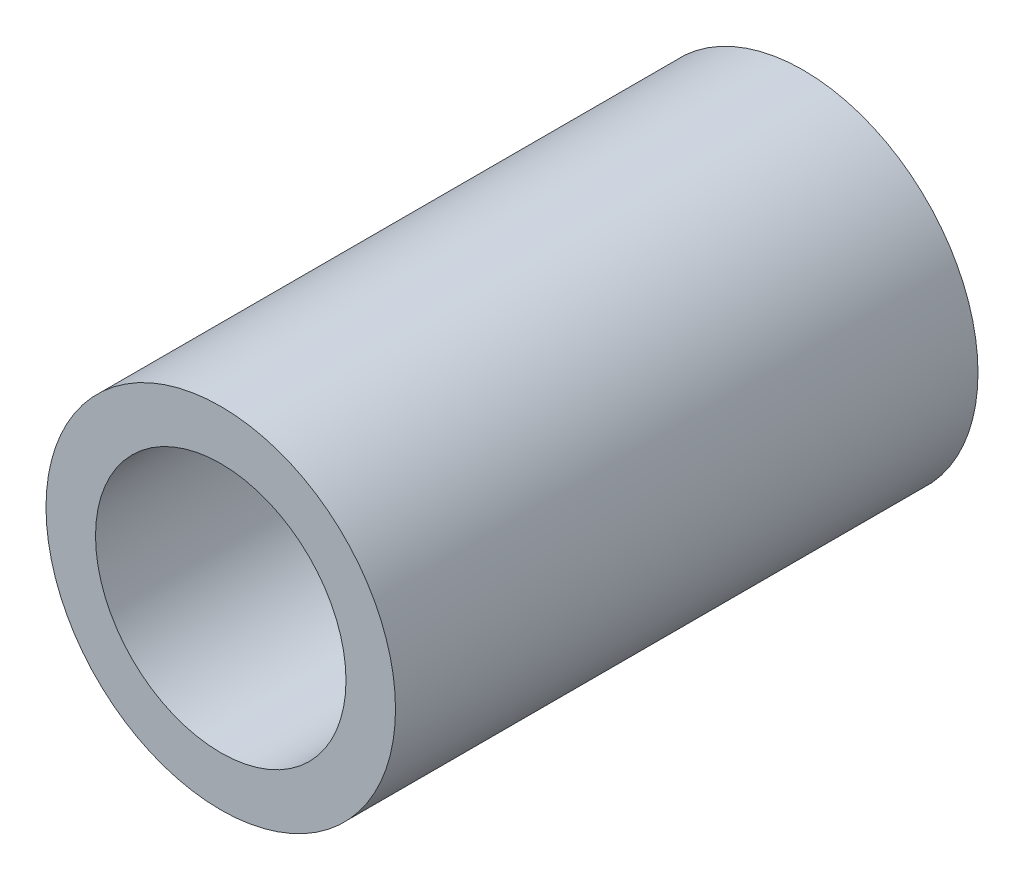
SolidWorks part; units mm, degrees
ref_plane "Front Plane" through (0, 0, 0) normal (0, 0, 1) x (1, 0, 0)
ref_plane "Top Plane" through (0, 0, 0) normal (0, 1, 0) x (1, 0, 0)
ref_plane "Right Plane" through (0, 0, 0) normal (1, 0, 0) x (0, 0, -1)
sketch "Sketch3" plane through (0, 0, 0) normal (0, 0, 1) x (1, 0, 0)
  circle A0 centre (0, 0) radius 2.15 construction
  circle A1 centre (0, 0) radius 3 construction
  point P6 (0, -2.15)
  dimension "OD" = 6
  dimension "ID" = 4.3
sketch "Sketch1" plane through (0, 0, 0) normal (1, 0, 0) x (0, 0, -1)
  line L0 (-5, -2.15) -> (-5, 2.15) construction
  line L1 (5, -3) -> (-5, -3) construction
  line L2 (5, -3) -> (5, 3) construction
  line L3 (5, 3) -> (-5, 3) construction
  line L4 (-5, -3) -> (-5, 3) construction
  line L5 (0, 3) -> (0, -3) construction
  line L6 (5, 0) -> (-5, 0) construction
  line L8 (0, 3) -> (0, -3) construction
  line L9 (-5, 2.15) -> (0, 2.15) construction
  point P0 (0, 0)
  point P7 (-5, 0)
  dimension "Length" = 10
sketch "Sketch2" plane through (0, 0, 0) normal (0, 0, 1) x (1, 0, 0)
  circle A0 centre (0, 0) radius 3
  circle A1 centre (0, 0) radius 2.15
extrude "Extrude1" add sketch "Sketch2" along normal up to vertex and the other way up to vertex up to point (0, -3, 5) other way up to point (0, 3, -5)
